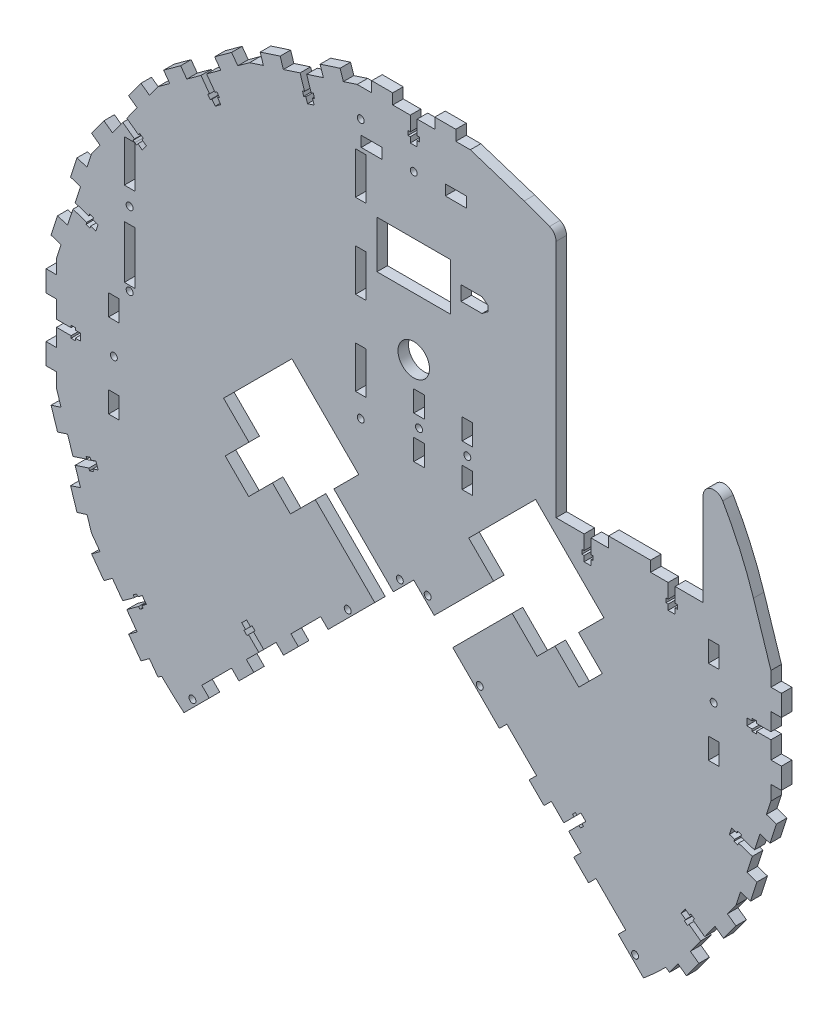
SolidWorks part; units mm, degrees
ref_plane "Front Plane" through (0, 0, 0) normal (0, 0, 1) x (1, 0, 0)
ref_plane "Top Plane" through (0, 0, 0) normal (0, 1, 0) x (1, 0, 0)
ref_plane "Right Plane" through (0, 0, 0) normal (1, 0, 0) x (0, 0, -1)
sketch "Sketch1" plane through (0, 0, 0) normal (0, 0, 1) x (1, 0, 0)
  circle A0 centre (0, 0) radius 215.9
  circle A1 centre (0, 0) radius 215.9 construction
extrude "Boss-Extrude1" add sketch "Sketch1" along normal blind 6.35 contours A0
sketch "Sketch2" plane through (0, 0, 0) normal (0, 0, -1) x (-1, 0, 0)
  line L0 (0, -26.4411) -> (138.8703, -165.3114)
  line L2 (0, -26.4411) -> (-138.8703, -165.3114)
  line L3 (-134.0557, -160.4967) -> (0, -26.4411) construction
  line L4 (0, 0) -> (0, -240.5018) construction
  arc A4 (-138.8703, -165.3114) -> (138.8703, -165.3114) centre (0, 0) ccw
  circle A5 centre (0, 0) radius 215.9 construction
  dimension "D1" = 90
extrude "Cut-Extrude1" cut sketch "Sketch2" against normal through all
sketch "Sketch3" plane through (0, 0, 6.35) normal (0, 0, 1) x (1, 0, 0)
  line L0 (73.6381, 52.5852) -> (114.9473, 11.276)
  line L1 (73.6381, 52.5852) -> (33.2269, 12.174)
  line L2 (114.9473, 11.276) -> (74.5361, -29.1352)
  line L3 (33.2269, 12.174) -> (74.5361, -29.1352)
  line L4 (74.5361, -29.1352) -> (70.046, -24.645) construction
  line L5 (97.2507, 34.8885) -> (46.1575, -16.2046) construction
  line L6 (48.2689, -2.8679) -> (59.4942, -14.0932)
  line L7 (48.2689, -2.8679) -> (12.3479, -38.7889)
  line L8 (59.4942, -14.0932) -> (23.5732, -50.0143)
  line L9 (12.3479, -38.7889) -> (23.5732, -50.0143)
  line L10 (88.68, 15.0926) -> (77.4547, 26.3179) construction
  line L11 (0, -26.4411) -> (138.8703, -165.3114) construction
  line M8 (0, -26.4411) -> (138.8703, -165.3114)
extrude "Cut-Extrude2" cut sketch "Sketch3" against normal through all contours L8 L6 L3 L7 M8 | L0 L5 L6 L3 L2 | L5 L0 L1 L3 region at (63.7598, 22.0523, 6.35) region at (84.4144, 1.3977, 6.35) region at (35.921, -26.4411, 6.35)
mirror "Mirror1" about plane through (0, 0, 0) normal (1, 0, 0) of "Cut-Extrude2"
sketch "Sketch4" plane through (0, 0, 6.35) normal (0, 0, 1) x (1, 0, 0)
  line L0 (-178.0884, 19.05) -> (-178.0884, 31.75) construction
  line L1 (178.0884, -19.05) -> (184.4384, -19.05)
  line L2 (178.0884, -19.05) -> (178.0884, -31.75)
  line L3 (178.0884, -31.75) -> (184.4384, -31.75)
  line L4 (184.4384, -19.05) -> (184.4384, -31.75)
  line L5 (178.0884, 31.75) -> (184.4384, 31.75)
  line L6 (178.0884, 31.75) -> (178.0884, 19.05)
  line L7 (178.0884, 19.05) -> (184.4384, 19.05)
  line L8 (184.4384, 31.75) -> (184.4384, 19.05)
  line L9 (178.0884, -19.05) -> (184.4384, -19.05)
  line L10 (178.0884, -19.05) -> (178.0884, -31.75)
  line L11 (178.0884, -31.75) -> (184.4384, -31.75)
  line L12 (184.4384, -19.05) -> (184.4384, -31.75)
  line L13 (-184.4384, 31.75) -> (-178.0884, 31.75)
  line L14 (-184.4384, 31.75) -> (-184.4384, 19.05)
  line L15 (-184.4384, 19.05) -> (-178.0884, 19.05)
  line L16 (-178.0884, 31.75) -> (-178.0884, 19.05)
  line L18 (-184.4384, -19.05) -> (-178.0884, -19.05)
  line L19 (-184.4384, -19.05) -> (-184.4384, -31.75)
  line L20 (-184.4384, -31.75) -> (-178.0884, -31.75)
  line L21 (-178.0884, -19.05) -> (-178.0884, -31.75)
extrude "Cut-Extrude3" cut sketch "Sketch4" against normal through all contours L21 L18 L19 L20 | L8 L5 L6 L7 | L4 L1 L2 L3 | L14 L15 L16 L13 region at (181.2634, -25.4, 6.35) region at (181.2634, 25.4, 6.35) region at (-181.2634, -25.4, 6.35)
sketch "Sketch5" plane through (0, 0, 6.35) normal (0, 0, 1) x (1, 0, 0)
  line L0 (-128.1057, -145.5666) -> (-110.1452, -127.6061)
  line L1 (-110.1452, -127.6061) -> (-105.6551, -132.0962)
  line L2 (-138.8703, -165.3114) -> (-23.5732, -50.0143) construction
  line L3 (-105.6551, -132.0962) -> (-110.1452, -127.6061) construction
  line L4 (-105.6551, -132.0962) -> (-123.6156, -150.0567)
  line L5 (-128.1057, -145.5666) -> (-123.6156, -150.0567) construction
  line L6 (-123.6156, -150.0567) -> (-128.1057, -145.5666)
extrude "Cut-Extrude4" cut sketch "Sketch5" against normal blind 6.35
pattern_linear "LPattern1" count 3 spacing 38.1 along (0.7071, 0.7071, 0) of "Cut-Extrude4"
sketch "Sketch6" plane through (0, 0, 6.35) normal (0, 0, 1) x (1, 0, 0)
  line L0 (110.1452, -127.6061) -> (128.1057, -145.5666)
  line L1 (128.1057, -145.5666) -> (123.6156, -150.0567)
  line L2 (23.5732, -50.0143) -> (138.8703, -165.3114) construction
  line L3 (123.6156, -150.0567) -> (128.1057, -145.5666) construction
  line L4 (123.6156, -150.0567) -> (105.6551, -132.0962)
  line L5 (110.1452, -127.6061) -> (105.6551, -132.0962) construction
  line L6 (105.6551, -132.0962) -> (110.1452, -127.6061)
extrude "Cut-Extrude5" cut sketch "Sketch6" against normal blind 6.35
pattern_linear "LPattern2" count 3 spacing 38.1 along (-0.7071, 0.7071, 0) of "Cut-Extrude5"
sketch "Sketch8" plane through (0, 0, 0) normal (0, 0, -1) x (-1, 0, 0)
  line L0 (174.9134, 48.3833) -> (174.9134, 73.7833) construction
  line L1 (28.8634, 181.7333) -> (35.2134, 181.7333)
  line L2 (28.8634, 181.7333) -> (28.8634, 156.3333)
  line L3 (28.8634, 156.3333) -> (35.2134, 156.3333)
  line L4 (35.2134, 181.7333) -> (35.2134, 156.3333)
  line L5 (28.8634, 130.9333) -> (35.2134, 130.9333)
  line L6 (28.8634, 130.9333) -> (28.8634, 105.5333)
  line L7 (28.8634, 105.5333) -> (35.2134, 105.5333)
  line L8 (35.2134, 130.9333) -> (35.2134, 105.5333)
  line L9 (28.8634, 80.1333) -> (35.2134, 80.1333)
  line L10 (28.8634, 80.1333) -> (28.8634, 54.7333)
  line L11 (28.8634, 54.7333) -> (35.2134, 54.7333)
  line L12 (35.2134, 80.1333) -> (35.2134, 54.7333)
  line L13 (168.5634, 118.2333) -> (174.9134, 118.2333)
  line L14 (168.5634, 118.2333) -> (168.5634, 92.8333)
  line L15 (168.5634, 92.8333) -> (174.9134, 92.8333)
  line L16 (174.9134, 118.2333) -> (174.9134, 92.8333)
  line L17 (168.5634, 73.7833) -> (174.9134, 73.7833)
  line L18 (168.5634, 73.7833) -> (168.5634, 41.9385)
  line L19 (168.5634, 41.9385) -> (174.9134, 41.9385)
  line L20 (174.9134, 73.7833) -> (174.9134, 41.9385)
extrude "Cut-Extrude7" cut sketch "Sketch8" against normal through all
sketch "Sketch11" plane through (0, 0, 0) normal (0, 0, -1) x (-1, 0, 0)
  line L0 (184.4384, 2.1209) -> (178.0884, -2.1209) construction
  line L1 (184.4384, -2.1209) -> (178.0884, 2.1209) construction
  circle A0 centre (181.2634, 0) radius 2.0955
  dimension "D1" = 4.191
extrude "Wheel Hole" cut sketch "Sketch11" against normal through all
mirror "Mirror2" about plane through (0, 0, 0) normal (1, 0, 0) of "Wheel Hole"
sketch "Sketch12" plane through (0, 0, 6.35) normal (0, 0, 1) x (1, 0, 0)
  line L0 (0, 0) -> (0, 252.4228) construction
  line L1 (22.225, 123.825) -> (-22.225, 123.825)
  line L2 (22.225, 123.825) -> (22.225, 152.4)
  line L3 (22.225, 152.4) -> (-22.225, 152.4)
  line L4 (-22.225, 123.825) -> (-22.225, 152.4)
  arc A0 (138.8703, -165.3114) -> (-138.8703, -165.3114) centre (0, 0) ccw construction
  dimension "D3" = 152.4
  dimension "D1" = 28.575
  dimension "D2" = 44.45
extrude "Battery hole" cut sketch "Sketch12" against normal through all
sketch "Sketch13" plane through (0, 0, 0) normal (0, 0, -1) x (-1, 0, 0)
  line L0 (137.5285, -154.9894) -> (130.021, -156.4621) construction
  line L1 (134.5112, -151.972) -> (130.021, -156.4621) construction
  line L2 (138.8703, -165.3114) -> (123.6156, -150.0567) construction
  line L3 (134.5112, -151.972) -> (133.0384, -159.4795) construction
  line L4 (137.5285, -154.9894) -> (133.0384, -159.4795) construction
  line L5 (36.1647, -62.6058) -> (43.6722, -61.133) construction
  line L6 (51.7736, -78.2147) -> (23.5732, -50.0143) construction
  line L7 (40.6548, -58.1157) -> (36.1647, -62.6058) construction
  line L8 (39.1821, -65.6231) -> (40.6548, -58.1157) construction
  line L9 (43.6722, -61.133) -> (39.1821, -65.6231) construction
  line L10 (4.6652, -31.1063) -> (12.1727, -29.6336) construction
  line L11 (12.3479, -38.7889) -> (0, -26.4411) construction
  line L12 (9.1554, -26.6162) -> (4.6652, -31.1063) construction
  line L13 (7.6826, -34.1237) -> (9.1554, -26.6162) construction
  line L14 (12.1727, -29.6336) -> (7.6826, -34.1237) construction
  circle A0 centre (133.7748, -155.7257) radius 2.0955
  circle A1 centre (39.9184, -61.8694) radius 2.0955
  circle A2 centre (8.419, -30.37) radius 2.0955
  dimension "D1" = 4.191
extrude "Cut-Extrude10" cut sketch "Sketch13" against normal through all
mirror "Mirror3" about plane through (0, 0, 0) normal (1, 0, 0) of "Cut-Extrude10"
sketch "Sketch14" plane through (0, 0, 6.35) normal (0, 0, 1) x (1, 0, 0)
  line L0 (-174.9134, 85.4419) -> (-168.5634, 81.1747) construction
  line L1 (-168.5634, 85.4419) -> (-174.9134, 81.1747) construction
  line L2 (-174.9134, 40.9919) -> (-168.5634, 36.7247) construction
  line L3 (-174.9134, 36.7247) -> (-168.5634, 40.9919) construction
  circle A0 centre (-171.7384, 83.3083) radius 2.0955
  circle A1 centre (-171.7384, 38.8583) radius 2.0955
  dimension "D1" = 4.191
extrude "Cut-Extrude11" cut sketch "Sketch14" against normal through all
sketch "Sketch15" plane through (0, 0, 6.35) normal (0, 0, 1) x (1, 0, 0)
  line L0 (-28.8634, 44.1669) -> (-35.2134, 39.8997) construction
  line L1 (-35.2134, 44.1669) -> (-28.8634, 39.8997) construction
  line L2 (-35.2134, 200.9503) -> (-28.8634, 196.6831) construction
  line L3 (-28.8634, 200.9503) -> (-35.2134, 196.6831) construction
  circle A0 centre (-32.0384, 42.0333) radius 2.0955
  circle A1 centre (-32.0384, 198.8167) radius 2.0955
  dimension "D1" = 4.191
extrude "Cut-Extrude12" cut sketch "Sketch15" against normal through all
ref_axis "Axis1" through (0, 0, 465.2086) along (0, 0, -1)
sketch "Sketch16" plane through (0, 0, 6.35) normal (0, 0, 1) x (1, 0, 0)
  line L0 (0, 0) -> (0, -233.9836) construction
  line L1 (154.5673, -154.5673) -> (152.3626, -152.9655)
  line L2 (-99.2383, -194.7662) -> (-34.1952, -215.9)
  line L3 (-34.1952, -215.9) -> (34.1952, -215.9)
  line L4 (34.1952, -215.9) -> (99.2383, -194.7662)
  line L5 (99.2383, -194.7662) -> (154.5673, -154.5673)
  line L6 (154.5673, -154.5673) -> (194.7662, -99.2383)
  line L7 (194.7662, -99.2383) -> (215.9, -34.1952)
  line L8 (215.9, -34.1952) -> (215.9, 34.1952)
  line L9 (215.9, 34.1952) -> (194.7662, 99.2383)
  line L10 (194.7662, 99.2383) -> (154.5673, 154.5673)
  line L11 (154.5673, 154.5673) -> (99.2383, 194.7662)
  line L12 (99.2383, 194.7662) -> (34.1952, 215.9)
  line L13 (34.1952, 215.9) -> (-34.1952, 215.9)
  line L14 (-34.1952, 215.9) -> (-99.2383, 194.7662)
  line L15 (-99.2383, 194.7662) -> (-154.5673, 154.5673)
  line L16 (-154.5673, 154.5673) -> (-194.7662, 99.2383)
  line L17 (-194.7662, 99.2383) -> (-215.9, 34.1952)
  line L18 (-215.9, 34.1952) -> (-215.9, -34.1952)
  line L19 (-215.9, -34.1952) -> (-194.7662, -99.2383)
  line L20 (-194.7662, -99.2383) -> (-154.5673, -154.5673)
  line L21 (-154.5673, -154.5673) -> (-99.2383, -194.7662)
  line L25 (-154.5673, -154.5673) -> (-152.3626, -152.9655)
  circle A0 centre (0, 0) radius 215.9
  arc A1 (138.8703, -165.3114) -> (-138.8703, -165.3114) centre (0, 0) ccw construction
  circle A2 centre (0, 0) radius 215.9 construction
extrude "Boss-Extrude4" add sketch "Sketch16" against normal up to surface (6.35 mm away) contours A0 L20 L21 | A0 L19 L20 | A0 L18 L19 | A0 L17 L18 | A0 L16 L17 | A0 L15 L16 | A0 L14 L15 | A0 L13 L14 | A0 L8 L9 | A0 L7 L8 | A0 L6 L7 | A0 L5 L6 | A0 L12 L13 region at (158.9251, -147.1799, 6.35) region at (192.8516, -98.2628, 6.35) region at (213.7776, -33.8591, 6.35) region at (213.7776, 33.8591, 6.35) region at (-158.9251, -147.1799, 6.35) region at (-192.8516, -98.2628, 6.35) region at (33.8591, 213.7776, 6.35) region at (-213.7776, -33.8591, 6.35) region at (-33.8591, 213.7776, 6.35) region at (-213.7776, 33.8591, 6.35) region at (-98.2628, 192.8516, 6.35) region at (-192.8516, 98.2628, 6.35) region at (-153.0479, 153.0479, 6.35) up to face at (-29.9429, 198.8167, 0)
sketch "Sketch17" plane through (174.6668, -126.9028, 0) normal (0.809, -0.5878, 0) x (0, 0, -1)
  line L0 (-6.35, -34.1952) -> (-6.35, 34.1952) construction
  line L1 (-6.35, -25.4) -> (0, -25.4)
  line L2 (-6.35, -25.4) -> (-6.35, -12.7)
  line L3 (-6.35, -12.7) -> (0, -12.7)
  line L4 (0, -25.4) -> (0, -12.7)
  line L7 (-6.35, 12.7) -> (0, 12.7)
  line L8 (-6.35, 12.7) -> (-6.35, 25.4)
  line L9 (-6.35, 25.4) -> (0, 25.4)
  line L10 (0, 12.7) -> (0, 25.4)
  line L11 (-17.1031, 0) -> (6.0458, 0) construction
  line L14 (0, -34.1952) -> (-6.35, -34.1952) construction
  line L15 (0, 34.1952) -> (-6.35, 34.1952) construction
  line L16 (0, 34.1952) -> (0, -34.1952) construction
  dimension "D1" = 25.4
  dimension "D2" = 12.7
extrude "Boss-Extrude5" add sketch "Sketch17" along normal blind 6.35
sketch "Sketch18" plane through (0, 0, 6.35) normal (0, 0, 1) x (1, 0, 0)
  line L0 (157.8586, -114.691) -> (174.6668, -126.9028) construction
  line L1 (167.2019, -137.1774) -> (182.1316, -116.6283) construction
  line L2 (172.3392, -140.9098) -> (167.2019, -137.1774) construction
  line L3 (187.2689, -120.3608) -> (182.1316, -116.6283) construction
  line B0 (173.4351, -128.5981) -> (175.8985, -125.2075)
  line B1 (166.7542, -118.5638) -> (167.538, -117.485)
  line B2 (167.538, -117.485) -> (169.5929, -118.978)
  line B3 (169.5929, -118.978) -> (168.8091, -120.0568)
  line B4 (168.8091, -120.0568) -> (175.8985, -125.2075)
  line B5 (166.7542, -118.5638) -> (164.0828, -116.6229)
  line B6 (164.0828, -116.6229) -> (161.6194, -120.0135)
  line B7 (164.2907, -121.9544) -> (161.6194, -120.0135)
  line B8 (166.3456, -123.4474) -> (173.4351, -128.5981)
  line B9 (165.5618, -124.5262) -> (166.3456, -123.4474)
  line B10 (163.5069, -123.0332) -> (165.5618, -124.5262)
  line B11 (164.2907, -121.9544) -> (163.5069, -123.0332)
sketch_block_instance "TSlot-1"
sketch_block "TSlot" parameters "D1"=3.302, "D2"=2.54, "D3"=3.175, "D4"=8.763, "D5"=1.3462
extrude "Cut-Extrude13" cut sketch "Sketch18" against normal through all
sketch "Sketch19" plane through (-174.6668, -126.9028, 0) normal (-0.809, -0.5878, 0) x (0, 0, 1)
  line L1 (6.35, 25.4) -> (0, 25.4)
  line L2 (6.35, 25.4) -> (6.35, 12.7)
  line L3 (6.35, 12.7) -> (0, 12.7)
  line L4 (0, 25.4) -> (0, 12.7)
  line L5 (6.35, 34.1952) -> (6.35, -34.1952) construction
  line L6 (0, 0) -> (10.0238, 0) construction
  line L7 (0, -25.4) -> (6.35, -25.4)
  line L8 (0, -25.4) -> (0, -12.7)
  line L9 (0, -12.7) -> (6.35, -12.7)
  line L10 (6.35, -25.4) -> (6.35, -12.7)
  line L13 (0, -34.1952) -> (0, 34.1952) construction
  dimension "D1" = 12.7
  dimension "D2" = 25.4
extrude "Boss-Extrude6" add sketch "Sketch19" along normal blind 6.35
sketch "Sketch20" plane through (0, 0, 6.35) normal (0, 0, 1) x (1, 0, 0)
  line L0 (-157.0104, -114.0748) -> (-191.0307, -138.792) construction
  line L1 (-187.2689, -120.3608) -> (-182.1316, -116.6283) construction
  line L2 (-172.3392, -140.9098) -> (-167.2019, -137.1774) construction
  line L3 (-182.1316, -116.6283) -> (-167.2019, -137.1774) construction
  line B0 (-175.8985, -125.2075) -> (-173.4351, -128.5981)
  line B1 (-164.2907, -121.9544) -> (-163.5069, -123.0332)
  line B2 (-163.5069, -123.0332) -> (-165.5618, -124.5262)
  line B3 (-165.5618, -124.5262) -> (-166.3456, -123.4474)
  line B4 (-166.3456, -123.4474) -> (-173.4351, -128.5981)
  line B5 (-164.2907, -121.9544) -> (-161.6194, -120.0135)
  line B6 (-161.6194, -120.0135) -> (-164.0828, -116.6229)
  line B7 (-166.7542, -118.5638) -> (-164.0828, -116.6229)
  line B8 (-168.8091, -120.0568) -> (-175.8985, -125.2075)
  line B9 (-169.5929, -118.978) -> (-168.8091, -120.0568)
  line B10 (-167.538, -117.485) -> (-169.5929, -118.978)
  line B11 (-166.7542, -118.5638) -> (-167.538, -117.485)
sketch_block_instance "TSlot-3"
extrude "Cut-Extrude14" cut sketch "Sketch20" against normal through all
pattern_circular "CirPattern2" count 8 every 18 about axis through (0, 0, 465.2086) along (0, 0, -1) of "Boss-Extrude6", "Cut-Extrude14"
pattern_circular "CirPattern3" count 3 every 18 about axis through (0, 0, 465.2086) along (0, 0, -1) of "Boss-Extrude5", "Cut-Extrude13" reverse direction yes
sketch "Sketch21" plane through (0, 0, 6.35) normal (0, 0, 1) x (1, 0, 0)
  line L0 (36.8153, 138.1125) -> (56.9261, 138.1125) construction
  line L1 (22.225, 152.4) -> (-22.225, 152.4) construction
  line L2 (-22.225, 123.825) -> (22.225, 123.825) construction
  line L3 (41.275, 142.494) -> (44.831, 139.7953)
  line L4 (28.575, 142.494) -> (41.275, 142.494)
  line L5 (28.575, 142.494) -> (28.575, 133.731)
  line L6 (28.575, 133.731) -> (41.275, 133.731)
  line L7 (41.275, 142.494) -> (41.275, 133.731)
  line L8 (44.831, 139.7953) -> (44.831, 136.4297)
  line L9 (44.831, 136.4297) -> (41.275, 133.731)
  line L10 (22.225, 123.825) -> (22.225, 152.4) construction
  dimension "D1" = 8.763
  dimension "D2" = 12.7
  dimension "D3" = 3.3655
  dimension "D4" = 16.256
  dimension "D5" = 6.35
extrude "XT60BatteryHole" cut sketch "Sketch21" against normal through all contours L7 L4 L5 L6 | L9 L8 L3 L7 | L7 L0 L8 L3 region at (42.7892, 139.7286, 6.35) region at (34.925, 138.1125, 6.35) region at (42.7892, 136.4964, 6.35)
sketch "Sketch22" plane through (0, 0, 6.35) normal (0, 0, 1) x (1, 0, 0)
  line L0 (0, 0) -> (0, 99.9362) construction
  line L1 (-53.4325, 88.9) -> (53.4325, 88.9) construction
  circle A0 centre (0, 88.9) radius 9.525
  dimension "D1" = 19.05
  dimension "D2" = 88.9
extrude "Wire Hole for Servo and Top Comps." cut sketch "Sketch22" against normal through all
sketch "Sketch23" plane through (0, 0, 0) normal (0, 0, -1) x (-1, 0, 0)
  line L1 (-35.56, 35.56) -> (-29.21, 35.56)
  line L2 (-35.56, 35.56) -> (-35.56, 48.26)
  line L3 (-35.56, 48.26) -> (-29.21, 48.26)
  line L4 (-29.21, 35.56) -> (-29.21, 48.26)
  line L5 (-35.56, 60.96) -> (-29.21, 60.96)
  line L6 (-35.56, 60.96) -> (-35.56, 73.66)
  line L7 (-35.56, 73.66) -> (-29.21, 73.66)
  line L8 (-29.21, 60.96) -> (-29.21, 73.66)
  line L9 (-6.35, 35.56) -> (0, 35.56)
  line L10 (-6.35, 35.56) -> (-6.35, 48.26)
  line L11 (-6.35, 48.26) -> (0, 48.26)
  line L12 (0, 35.56) -> (0, 48.26)
  line L13 (-6.35, 60.96) -> (0, 60.96)
  line L14 (-6.35, 60.96) -> (-6.35, 73.66)
  line L15 (-6.35, 73.66) -> (0, 73.66)
  line L16 (0, 60.96) -> (0, 73.66)
extrude "CameraMountTabHoles" cut sketch "Sketch23" against normal through all
sketch "Sketch24" plane through (0, 0, 6.35) normal (0, 0, 1) x (1, 0, 0)
  line L0 (29.21, 56.7436) -> (35.56, 52.4764) construction
  line L1 (29.21, 52.4764) -> (35.56, 56.7436) construction
  line L2 (0, 56.7436) -> (6.35, 52.4764) construction
  line L3 (6.35, 56.7436) -> (0, 52.4764) construction
  circle A0 centre (32.385, 54.61) radius 2.0955
  circle A1 centre (3.175, 54.61) radius 2.0955
  dimension "D1" = 4.191
extrude "Cut-Extrude18" cut sketch "Sketch24" against normal through all
sketch "Sketch25" plane through (0, 0, 6.35) normal (0, 0, 1) x (1, 0, 0)
  line L1 (-31.75, 190.5) -> (-19.05, 190.5)
  line L2 (-31.75, 190.5) -> (-31.75, 184.15)
  line L3 (-31.75, 184.15) -> (-19.05, 184.15)
  line L4 (-19.05, 190.5) -> (-19.05, 184.15)
  line L5 (19.05, 190.5) -> (31.75, 190.5)
  line L6 (19.05, 190.5) -> (19.05, 184.15)
  line L7 (19.05, 184.15) -> (31.75, 184.15)
  line L8 (31.75, 190.5) -> (31.75, 184.15)
extrude "Cut-Extrude19" cut sketch "Sketch25" against normal through all
sketch "Sketch26" plane through (0, 0, 0) normal (0, 0, -1) x (-1, 0, 0)
  line L0 (-2.1336, 184.15) -> (2.1336, 190.5) construction
  line L1 (-2.1336, 190.5) -> (2.1336, 184.15) construction
  circle A0 centre (0, 187.325) radius 2.0955
  dimension "D1" = 4.191
extrude "Cut-Extrude20" cut sketch "Sketch26" against normal through all
sketch "Sketch27" plane through (0, 0, 6.35) normal (0, 0, 1) x (1, 0, 0)
  line L0 (167.1371, -38.3935) -> (160.7871, -34.1263) construction
  line L1 (167.1371, -34.1263) -> (160.7871, -38.3935) construction
  line L2 (167.1371, 58.5607) -> (160.7871, 62.8279) construction
  line L3 (167.1371, 62.8279) -> (160.7871, 58.5607) construction
  circle A0 centre (163.9621, 60.6943) radius 2.0955
  circle A1 centre (163.9621, -36.2599) radius 2.0955
  dimension "D1" = 4.191
extrude "Cut-Extrude21" [suppressed] cut sketch "Sketch27" against normal through all
sketch "Sketch28" plane through (0, 0, 6.35) normal (0, 0, 1) x (1, 0, 0)
  line L0 (28.2358, 111.125) -> (23.9686, 104.775) construction
  line L1 (23.9686, 111.125) -> (28.2358, 104.775) construction
  line L2 (125.19, 111.125) -> (120.9228, 104.775) construction
  line L3 (120.9228, 111.125) -> (125.19, 104.775) construction
  circle A0 centre (123.0564, 107.95) radius 2.0955
  circle A1 centre (26.1022, 107.95) radius 2.0955
  dimension "D1" = 4.191
extrude "Cut-Extrude22" [suppressed] cut sketch "Sketch28" against normal through all
sketch "Sketch29" plane through (0, 0, 0) normal (0, 0, -1) x (-1, 0, 0)
  line L1 (-167.1371, -11.1125) -> (-160.7871, -11.1125)
  line L2 (-167.1371, -11.1125) -> (-167.1371, 26.9875)
  line L3 (-167.1371, 26.9875) -> (-160.7871, 26.9875)
  line L4 (-160.7871, -11.1125) -> (-160.7871, 26.9875)
  line L5 (-89.3496, 111.125) -> (-51.2496, 111.125)
  line L6 (-89.3496, 111.125) -> (-89.3496, 104.775)
  line L7 (-89.3496, 104.775) -> (-51.2496, 104.775)
  line L8 (-51.2496, 111.125) -> (-51.2496, 104.775)
extrude "Cut-Extrude23" [suppressed] cut sketch "Sketch29" against normal through all
sketch "Sketch30" plane through (0, 0, 6.35) normal (0, 0, 1) x (1, 0, 0)
  line L0 (-92.1847, -109.6456) -> (-120.1804, -81.6499) construction
  line L1 (-83.2045, -100.6653) -> (-101.165, -118.6258) construction
  line L2 (-83.2045, -100.6653) -> (-101.165, -118.6258) construction
  line B0 (-93.6665, -111.1273) -> (-90.703, -108.1638)
  line B1 (-98.6954, -100.1714) -> (-97.7525, -99.2285)
  line B2 (-97.7525, -99.2285) -> (-95.9564, -101.0245)
  line B3 (-95.9564, -101.0245) -> (-96.8994, -101.9674)
  line B4 (-96.8994, -101.9674) -> (-90.703, -108.1638)
  line B5 (-98.6954, -100.1714) -> (-101.0303, -97.8365)
  line B6 (-101.0303, -97.8365) -> (-103.9938, -100.8)
  line B7 (-101.6589, -103.1349) -> (-103.9938, -100.8)
  line B8 (-99.8628, -104.9309) -> (-93.6665, -111.1273)
  line B9 (-100.8058, -105.8739) -> (-99.8628, -104.9309)
  line B10 (-102.6018, -104.0778) -> (-100.8058, -105.8739)
  line B11 (-101.6589, -103.1349) -> (-102.6018, -104.0778)
sketch_block_instance "TSlot-4"
extrude "Cut-Extrude24" cut sketch "Sketch30" against normal through all
mirror "Mirror4" about plane through (0, 0, 0) normal (1, 0, 0) of "Cut-Extrude24"
sketch "Sketch31" plane through (0, 0, 6.35) normal (0, 0, 1) x (1, 0, 0)
  line L0 (-99.591, -4.0803) -> (-85.4022, -18.2691)
  line L1 (-99.591, -4.0803) -> (-113.9595, -18.4487)
  line L2 (-85.4022, -18.2691) -> (-99.7706, -32.6375)
  line L3 (-113.9595, -18.4487) -> (-99.7706, -32.6375)
  line L4 (-114.9473, 11.276) -> (-74.5361, -29.1352) construction
  line L5 (-112.8988, -17.388) -> (-88.3298, 7.181) construction
  line L6 (-74.141, -7.0078) -> (-98.71, -31.5768) construction
  line L7 (-100.8313, -31.5768) -> (-112.8988, -19.5093) construction
  line L8 (99.591, -4.0803) -> (85.4022, -18.2691)
  line L9 (99.591, -4.0803) -> (113.9595, -18.4487)
  line L10 (85.4022, -18.2691) -> (99.7706, -32.6375)
  line L11 (113.9595, -18.4487) -> (99.7706, -32.6375)
  line L12 (114.9473, 11.276) -> (74.5361, -29.1352) construction
  line L14 (98.71, -31.5768) -> (74.141, -7.0078) construction
  line L15 (112.8988, -19.5093) -> (100.8313, -31.5768) construction
  line L16 (88.3298, 7.181) -> (112.8988, -17.388) construction
extrude "Cut-Extrude25" cut sketch "Sketch31" against normal through all
sketch "Sketch32" plane through (0, 0, 6.35) normal (0, 0, 1) x (1, 0, 0)
  line L0 (178.0884, 31.75) -> (178.0884, 19.05) construction
  line L1 (86.0134, 138.0901) -> (174.9134, 138.0901)
  line L2 (86.0134, 138.0901) -> (86.0134, 49.1901)
  line L3 (86.0134, 49.1901) -> (174.9134, 49.1901)
  line L4 (174.9134, 138.0901) -> (174.9134, 49.1901)
  line L5 (73.6381, 52.5852) -> (114.9473, 11.276) construction
  line L6 (86.0134, 138.0901) -> (86.0134, 198.0265)
  arc A0 (205.3331, 66.7168) -> (66.7168, 205.3331) centre (0, 0) ccw construction
  arc A1 (86.0134, 198.0265) -> (165.9637, 138.0901) centre (0, 0) cw
  dimension "D1" = 88.9
  dimension "D2" = 3.175
  dimension "D3" = 6.35
extrude "Cut-Extrude26" cut sketch "Sketch32" against normal through all contours A1 L6 L1 | L4 L1 L2 L3 region at (114.7325, 159.7355, 6.35) region at (130.4634, 93.6401, 6.35)
sketch "Sketch33" plane through (0, 0, 6.35) normal (0, 0, 1) x (1, 0, 0)
  line L0 (86.0134, 49.1901) -> (174.9134, 49.1901) construction
  line L1 (117.7634, 49.1901) -> (143.1634, 49.1901)
  line L2 (117.7634, 49.1901) -> (117.7634, 55.5401)
  line L3 (117.7634, 55.5401) -> (143.1634, 55.5401)
  line L4 (143.1634, 49.1901) -> (143.1634, 55.5401)
  line L5 (174.9134, 55.5401) -> (86.0134, 55.5401) construction
  line L6 (130.4634, 22.6576) -> (130.4634, 86.4746) construction
  line L7 (86.0134, 49.1901) -> (86.0134, 198.0265) construction
  line L8 (174.9134, 126.5626) -> (174.9134, 49.1901) construction
  dimension "D1" = 25.4
extrude "Boss-Extrude7" add sketch "Sketch33" against normal up to surface (6.35 mm away) up to face at (-2.0955, 187.325, 0)
sketch "Sketch34" plane through (0, 0, 6.35) normal (0, 0, 1) x (1, 0, 0)
  line L3 (143.1634, 49.1901) -> (174.9134, 49.1901) construction
  line L5 (86.0134, 49.1901) -> (117.7634, 49.1901) construction
  line L7 (143.1634, 49.1901) -> (143.1634, 55.5401) construction
  line L8 (168.5634, 131.7401) -> (168.5634, 55.5401) construction
  line L9 (92.3634, 55.5401) -> (92.3634, 131.7401) construction
  line L10 (117.7634, 55.5401) -> (117.7634, 49.1901) construction
  line B0 (157.9589, 49.1901) -> (153.7679, 49.1901)
  line B1 (153.7679, 37.8871) -> (152.4344, 37.8871)
  line B2 (152.4344, 37.8871) -> (152.4344, 40.4271)
  line B3 (152.4344, 40.4271) -> (153.7679, 40.4271)
  line B4 (153.7679, 40.4271) -> (153.7679, 49.1901)
  line B5 (153.7679, 37.8871) -> (153.7679, 34.5851)
  line B6 (153.7679, 34.5851) -> (157.9589, 34.5851)
  line B7 (157.9589, 37.8871) -> (157.9589, 34.5851)
  line B8 (157.9589, 40.4271) -> (157.9589, 49.1901)
  line B9 (159.2924, 40.4271) -> (157.9589, 40.4271)
  line B10 (159.2924, 37.8871) -> (159.2924, 40.4271)
  line B11 (157.9589, 37.8871) -> (159.2924, 37.8871)
  line B12 (155.8634, 49.1901) -> (155.8634, 34.5851) construction
  line B13 (107.1589, 49.1901) -> (102.9679, 49.1901)
  line B14 (102.9679, 37.8871) -> (101.6344, 37.8871)
  line B15 (101.6344, 37.8871) -> (101.6344, 40.4271)
  line B16 (101.6344, 40.4271) -> (102.9679, 40.4271)
  line B17 (102.9679, 40.4271) -> (102.9679, 49.1901)
  line B18 (102.9679, 37.8871) -> (102.9679, 34.5851)
  line B19 (102.9679, 34.5851) -> (107.1589, 34.5851)
  line B20 (107.1589, 37.8871) -> (107.1589, 34.5851)
  line B21 (107.1589, 40.4271) -> (107.1589, 49.1901)
  line B22 (108.4924, 40.4271) -> (107.1589, 40.4271)
  line B23 (108.4924, 37.8871) -> (108.4924, 40.4271)
  line B24 (107.1589, 37.8871) -> (108.4924, 37.8871)
  line B25 (105.0634, 49.1901) -> (105.0634, 34.5851) construction
sketch_block_instance "TSlot-5"
sketch_block_instance "TSlot-6"
extrude "Cut-Extrude27" cut sketch "Sketch34" against normal through all
fillet "Fillet1" radius 6.35 2 edges at (86.0134, 198.0265, 3.175) (174.9134, 126.5626, 3.175)
